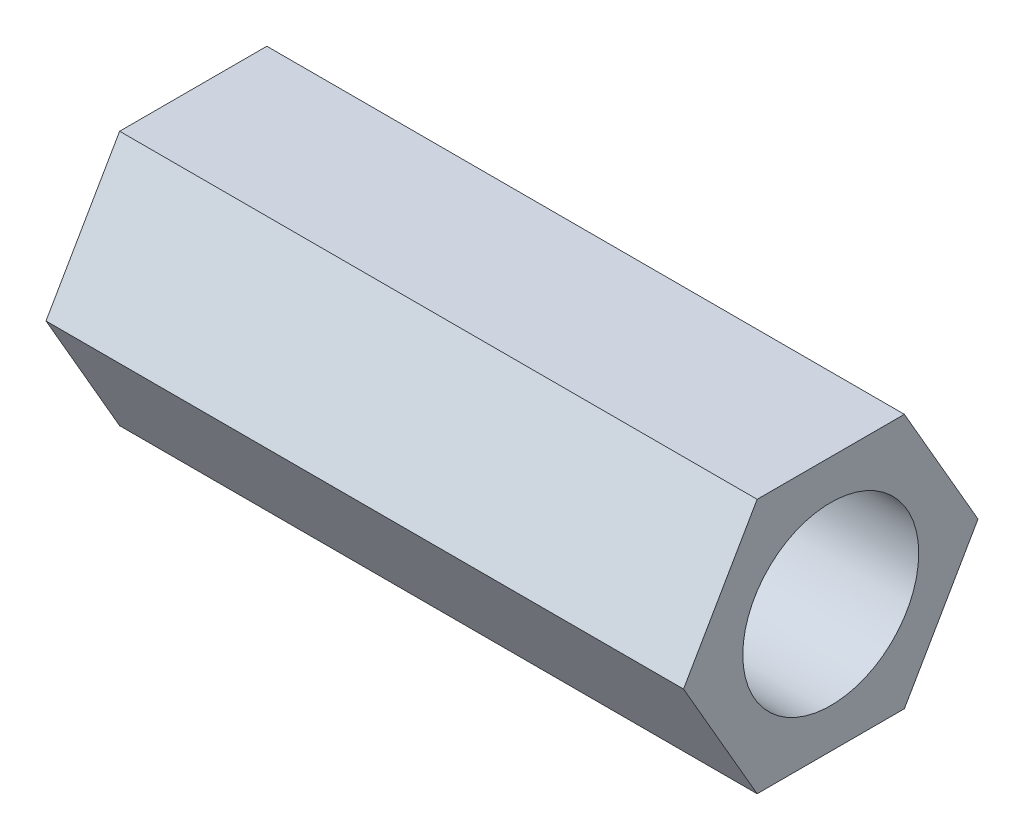
SolidWorks part; units mm, degrees
ref_plane "Front" through (0, 0, 0) normal (0, 0, 1) x (1, 0, 0)
ref_plane "Top" through (0, 0, 0) normal (0, 1, 0) x (1, 0, 0)
ref_plane "Right" through (0, 0, 0) normal (1, 0, 0) x (0, 0, -1)
sketch "Sketch1" plane through (0, 0, 0) normal (1, 0, 0) x (0, 0, -1)
  line L1 (7.3323, 0) -> (3.6662, 6.35)
  line L2 (3.6662, 6.35) -> (-3.6662, 6.35)
  line L3 (-3.6662, 6.35) -> (-7.3323, 0)
  line L4 (-7.3323, 0) -> (-3.6662, -6.35)
  line L5 (-3.6662, -6.35) -> (3.6662, -6.35)
  line L6 (3.6662, -6.35) -> (7.3323, 0)
  circle A0 centre (0, 0) radius 6.35 construction
  dimension "D1" = 12.7
extrude "Boss-Extrude1" add sketch "Sketch1" along normal blind 31.75
sketch "Sketch2" plane through (31.75, 0, 0) normal (1, 0, 0) x (0, 0, -1)
  circle A0 centre (0, 0) radius 4.381
  dimension "D1" = 8.762
extrude "Cut-Extrude1" cut sketch "Sketch2" against normal through all
